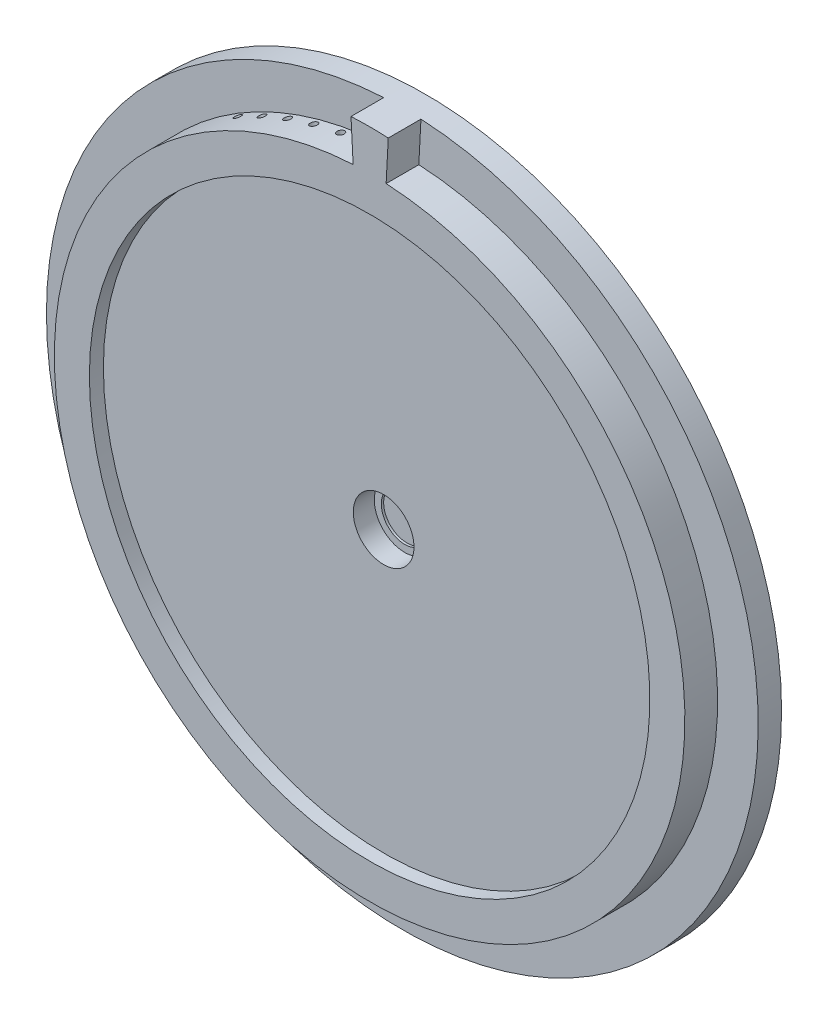
SolidWorks part; units mm, degrees
note: The reader was unsure of these and kept them because the rebuilt part matched: shared geometry of "Sketch1<3>".
ref_plane "Front Plane" through (0, 0, 0) normal (1, 0, 0) x (0, 1, 0)
ref_plane "Top Plane" through (0, 0, 0) normal (0, 0, 1) x (0, 1, 0)
ref_plane "Right Plane" through (0, 0, 0) normal (0, 1, 0) x (-1, 0, 0)
sketch "Sketch1" plane through (0, 0, 0) normal (1, 0, 0) x (0, 1, 0)
  line L0 (13, 13) -> (13, 4)
  line L2 (0, 3) -> (0, 0)
  line L4 (152.39, -5) -> (152.39, 5)
  line L6 (135, 19) -> (120, 19)
  line L7 (120, 19) -> (120, 13)
  line L8 (120, 13) -> (13, 13)
  line L9 (0, 0) -> (0, 38.0007) construction
  line L10 (135, 19) -> (135, 5)
  line L11 (135, 5) -> (152.39, 5)
  line L12 (135, 19) -> (152.39, 19)
  line L13 (152.39, 19) -> (152.39, 5)
  line L14 (135, 19) -> (152.39, 5) construction
  line L15 (0, 3) -> (10, 3)
  line L16 (10, 3) -> (10, 4)
  line L17 (10, 4) -> (13, 4)
  line L18 (0, 0) -> (19, 0)
  line L19 (19, 0) -> (19, 10)
  line L20 (19, 10) -> (129, 10)
  line L21 (129, 10) -> (129, -5)
  line L22 (129, -5) -> (152.39, -5)
  dimension "D1" = 1
  dimension "D2" = 9
  dimension "D3" = 26
  dimension "D4" = 6
  dimension "D5" = 14
  dimension "D6" = 3
  dimension "D7" = 120
  dimension "D8" = 304.78
  dimension "D9" = 20
  dimension "D10" = 6
  dimension "D11" = 3
  dimension "D12" = 135
  dimension "D13" = 10
  dimension "D14" = 6
revolve "Revolve1" add sketch "Sketch1" angle 360 about L9
revolve "Revolve2" add sketch "Sketch1<3>" angle 3 about L9
sketch "Sketch1<3>" plane through (0, 0, 0) normal (1, 0, 0) x (0, 1, 0) same geometry as "Sketch1"
ref_plane "Plane1" through (0, 0, 8) normal (0, 0, 1) x (0, -1, 0)
sketch "Sketch2" plane through (0, 0, 8) normal (0, 0, 1) x (0, 1, 0)
  line L2 (153.39, 0) -> (153.39, 4.7625)
  line L3 (153.39, 4.7625) -> (144.0593, 4.7625)
  line L5 (144.0593, 4.7625) -> (143.39, 0)
  line L9 (143.39, 0) -> (153.39, 0)
  line L14 (111.824, 11.3769) -> (151.6718, 14.8631)
  line L15 (111.824, 11.3769) -> (111.9623, 9.7954)
  line L16 (151.6718, 14.8631) -> (151.8101, 13.2817)
  line L17 (111.9623, 9.7954) -> (151.8101, 13.2817)
  arc A1 (152.1812, 7.9755) -> (152.1812, -7.9755) centre (0, 0) ccw construction
  arc A2 (152.1812, -7.9755) -> (152.1812, 7.9755) centre (0, 0) ccw construction
  point P3 (152.39, 0)
  dimension "D9" = 5
  dimension "D10" = 1.5875
  dimension "D11" = 40
  dimension "D2" = 1
  dimension "D3" = 82
  dimension "D4" = 10
  dimension "D8" = 4.7625
revolve "Cut-Revolve4" cut sketch "Sketch2" angle 360 about L17
pattern_circular "CirPattern1" count 6 every 5 about axis through (0, 0, 0) along (0, 0, -1) of "Cut-Revolve4"
